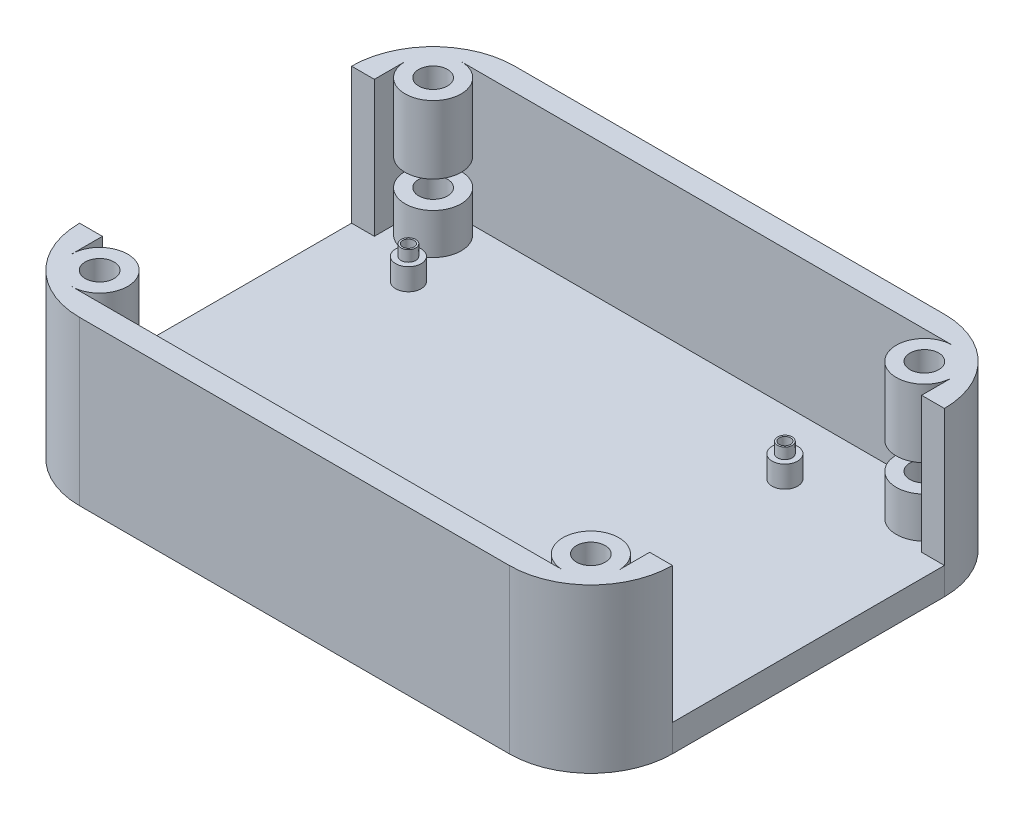
SolidWorks part; units mm, degrees
ref_plane "Front Plane" through (0, 0, 0) normal (0, 0, 1) x (1, 0, 0)
ref_plane "Top Plane" through (0, 0, 0) normal (0, 1, 0) x (1, 0, 0)
ref_plane "Right Plane" through (0, 0, 0) normal (1, 0, 0) x (0, 0, -1)
sketch "Sketch1" plane through (0, 0, 0) normal (0, 1, 0) x (1, 0, 0)
  line L0 (-39.5, 33) -> (39.5, 33)
  line L1 (-39.5, 28) -> (39.5, 28)
  line L2 (-42.5, 25) -> (-42.5, -25)
  line L3 (-39.5, -28) -> (39.5, -28)
  line L4 (42.5, 25) -> (42.5, -25)
  line L5 (-42.5, 28) -> (42.5, -28) construction
  line L6 (-42.5, -28) -> (42.5, 28) construction
  line L7 (47.5, 25) -> (47.5, -25)
  line L8 (-39.5, -33) -> (39.5, -33)
  line L9 (-47.5, 25) -> (-47.5, -25)
  line L10 (-39.5, 40) -> (39.5, 40)
  line L11 (54.5, 25) -> (54.5, -25)
  line L12 (-39.5, -40) -> (39.5, -40)
  line L13 (-54.5, 25) -> (-54.5, -25)
  arc A0 (-42.5, -25) -> (-39.5, -28) centre (-39.5, -25) ccw
  arc A1 (39.5, -28) -> (42.5, -25) centre (39.5, -25) ccw
  arc A2 (39.5, 28) -> (42.5, 25) centre (39.5, 25) cw
  arc A3 (-39.5, 28) -> (-42.5, 25) centre (-39.5, 25) ccw
  arc A4 (39.5, 33) -> (47.5, 25) centre (39.5, 25) cw
  arc A5 (39.5, -33) -> (47.5, -25) centre (39.5, -25) ccw
  arc A6 (-47.5, -25) -> (-39.5, -33) centre (-39.5, -25) ccw
  arc A7 (-39.5, 33) -> (-47.5, 25) centre (-39.5, 25) ccw
  arc A8 (39.5, 40) -> (54.5, 25) centre (39.5, 25) cw
  arc A9 (39.5, -40) -> (54.5, -25) centre (39.5, -25) ccw
  arc A10 (-54.5, -25) -> (-39.5, -40) centre (-39.5, -25) ccw
  arc A11 (-39.5, 40) -> (-54.5, 25) centre (-39.5, 25) ccw
  point P0 (0, 0)
  point P9 (0, 0)
  dimension "D3" = 3
  dimension "D1" = 85
  dimension "D2" = 56
  dimension "D4" = 5
  dimension "D5" = 7
extrude "Boss-Extrude1" add sketch "Sketch1" along normal blind 5 contours L0 A7 L9 A6 L8 A5 L7 A4 A3 L1 A2 L4 A1 L3 A0 L2 | L10 A11 L13 A10 L12 A9 L11 A8 A7 L0 A4 L7 A5 L8 A6 L9 | L2 A0 L3 A1 L4 A2 L1 A3 region at (0, 0, -31.8432) region at (0, 0, -38.6479)
sketch "Sketch4" plane through (0, 0, 0) normal (0, 1, 0) x (1, 0, 0)
  line L0 (-50.1066, 35.6066) -> (50.1066, -35.6066) construction
  line L1 (-17.5, 17.5) -> (17.5, 17.5) construction
  line L2 (-17.5, 17.5) -> (-17.5, -17.5) construction
  line L3 (-17.5, -17.5) -> (17.5, -17.5) construction
  line L4 (17.5, 17.5) -> (17.5, -17.5) construction
  line L5 (-17.5, 17.5) -> (17.5, -17.5) construction
  line L6 (-17.5, -17.5) -> (17.5, 17.5) construction
  line L7 (-50.1066, -35.6066) -> (50.1066, 35.6066) construction
  line L8 (-37.5, 26.6481) -> (-37.5, -26.6481) construction
  line L9 (-37.5, -26.6481) -> (37.5, -26.6481) construction
  line L10 (37.5, -26.6481) -> (37.5, 26.6481) construction
  line L11 (37.5, 26.6481) -> (-37.5, 26.6481) construction
  circle A0 centre (0, 0) radius 3.1
  circle A1 centre (17.5, -17.5) radius 3.1
  circle A2 centre (-17.5, -17.5) radius 3.1
  circle A3 centre (-17.5, 17.5) radius 3.1
  circle A4 centre (17.5, 17.5) radius 3.1
  circle A5 centre (-17.5, 0) radius 3.1
  circle A6 centre (0, 17.5) radius 3.1
  circle A7 centre (17.5, 0) radius 3.1
  circle A8 centre (0, -17.5) radius 3.1
  arc A9 (-39.5, 40) -> (-54.5, 25) centre (-39.5, 25) ccw construction
  arc A10 (39.5, -40) -> (54.5, -25) centre (39.5, -25) ccw construction
  arc A11 (-54.5, -25) -> (-39.5, -40) centre (-39.5, -25) ccw construction
  arc A12 (54.5, 25) -> (39.5, 40) centre (39.5, 25) ccw construction
  circle A13 centre (-37.5, 26.6481) radius 3.1
  circle A14 centre (37.5, 26.6481) radius 3.1
  circle A15 centre (-37.5, -26.6481) radius 3.1
  circle A16 centre (37.5, -26.6481) radius 3.1
  point P0 (0, 0)
  dimension "D1" = 6.2
  dimension "D2" = 6.2
  dimension "D3" = 6.2
  dimension "D4" = 6.2
  dimension "D5" = 6.2
  dimension "D7" = 6.2
  dimension "D8" = 6.2
  dimension "D9" = 6.2
  dimension "D10" = 6.2
  dimension "D11" = 6.2
  dimension "D12" = 6.2
  dimension "D13" = 6.2
  dimension "D14" = 6.2
  dimension "D6" = 35
  dimension "D15" = 75
extrude "Cut-Extrude1" cut sketch "Sketch4" along normal blind 4 contours A15 | A16 | A14 | A13 | A5 | A8 | A7 | A6 | A3 | A4 | A1 | A2 | A0 region at (-17.5, 0, 0) region at (0, 0, -17.5) region at (17.5, 0, 0) region at (0, 0, 17.5) region at (-37.5, 0, -26.6481) region at (37.5, 0, -26.6481) region at (-37.5, 0, 26.6481) region at (37.5, 0, 26.6481)
extrude "Boss-Extrude3" add sketch "Sketch1<3>" along normal blind 30 contours L10 A11 L13 A10 L12 A9 L11 A8 A7 L0 A4 L7 A5 L8 A6 L9 region at (0, 0, -38.6479)
sketch "Sketch1<3>" plane through (0, 0, 0) normal (0, 1, 0) x (1, 0, 0) same geometry as "Sketch1"
sketch "Sketch7" plane through (-54.5, 0, 0) normal (-1, 0, 0) x (0, 0, 1)
  line L0 (-20, 30) -> (-25, 30)
  line L1 (-25, 30) -> (-25, 0) construction
  line L2 (20, 30) -> (25, 30)
  line L3 (25, 30) -> (25, 0) construction
  line L4 (20, 5) -> (25, 5)
  line L5 (-20, 5) -> (-25, 5)
  line L6 (-25, 30) -> (-25, 5)
  line L7 (25, 30) -> (25, 5)
  line L8 (-25, 30) -> (25, 30) construction
  line L14 (-20, 5) -> (20, 5)
  line L15 (20, 5) -> (20, 25)
  line L16 (20, 25) -> (-20, 25)
  line L17 (-20, 25) -> (-20, 5)
  line L18 (-20, 5) -> (20, 5)
  line L20 (20, 30) -> (-20, 30)
  dimension "D1" = 5
extrude "Cut-Extrude2" cut sketch "Sketch7" against normal through all both and the other way through all
sketch "Sketch3" plane through (0, 0, 0) normal (0, 1, 0) x (1, 0, 0)
  line L0 (-40, 0) -> (26.04, 0) construction
  line L1 (-40, -20.955) -> (-40, 20.955) construction
  line L2 (26.04, -24.13) -> (26.04, 24.13) construction
  line L3 (-47.5, 25) -> (-47.5, -25) construction
  line L4 (-47.5, 0) -> (-40, 0) construction
  circle A0 centre (-40, 20.955) radius 1.35
  circle A1 centre (-40, -20.955) radius 1.35
  circle A2 centre (26.04, 24.13) radius 1.35
  circle A3 centre (26.04, -24.13) radius 1.35
  circle A4 centre (-40, -20.955) radius 1.05
  circle A5 centre (-40, 20.955) radius 1.05
  circle A6 centre (26.04, 24.13) radius 1.05
  circle A7 centre (26.04, -24.13) radius 1.05
  arc A8 (-47.5, -25) -> (-39.5, -33) centre (-39.5, -25) ccw construction
  arc A9 (-47.5, -25) -> (-39.5, -33) centre (-39.5, -25) ccw
  arc A10 (-39.5, 33) -> (-47.5, 25) centre (-39.5, 25) ccw construction
  arc A11 (-39.5, 33) -> (-47.5, 25) centre (-39.5, 25) ccw
  point P4 (-6.98, 0)
  point P8 (-40, 0)
  point P13 (26.04, 0)
  dimension "D4" = 2.7
  dimension "D5" = 2.7
  dimension "D6" = 2.7
  dimension "D7" = 2.7
  dimension "D9" = 2.1
  dimension "D10" = 2.1
  dimension "D11" = 2.1
  dimension "D12" = 2.1
  dimension "D1" = 66.04
  dimension "D2" = 48.26
  dimension "D3" = 41.91
  dimension "D8" = 7.5
extrude "Boss-Extrude2" add sketch "Sketch3" along normal blind 6 from surface contours A2 | A0 | A1 | A3 | A7 | A4 | A5 region at (24.7282, 0, -24.13) starting at face at (0, 5, 0)
sketch "Sketch8" plane through (0, 0, 0) normal (0, 1, 0) x (1, 0, 0)
  line L0 (0, 40) -> (0, 33) construction
  line L1 (-39.5, 40) -> (39.5, 40) construction
  line L2 (39.5, 33) -> (-39.5, 33) construction
  line L3 (-5, 36.5) -> (5, 36.5) construction
  circle A0 centre (5, 36.5) radius 3.1
  circle A1 centre (-5, 36.5) radius 2
  point P10 (0, 36.5)
  dimension "D2" = 6.2
  dimension "D3" = 4
  dimension "D1" = 10
sketch "Sketch13" plane through (0, 5, 0) normal (0, 1, 0) x (1, 0, 0)
  circle A0 centre (26.04, 24.13) radius 1.35 construction
  circle A1 centre (26.04, -24.13) radius 1.35 construction
  circle A2 centre (-40, -20.955) radius 1.35 construction
  circle A3 centre (-40, 20.955) radius 1.35 construction
  circle A4 centre (26.04, 24.13) radius 1.35
  circle A5 centre (26.04, -24.13) radius 1.35
  circle A6 centre (-40, -20.955) radius 1.35
  circle A7 centre (-40, 20.955) radius 1.35
  circle A8 centre (26.04, 24.13) radius 2.35
  circle A9 centre (26.04, -24.13) radius 2.35
  circle A10 centre (-40, -20.955) radius 2.35
  circle A11 centre (-40, 20.955) radius 2.35
  dimension "D1" = 1
  dimension "D2" = 1
extrude "Boss-Extrude8" add sketch "Sketch13" along normal blind 4
sketch "Sketch14" plane through (0, 30, 0) normal (0, 1, 0) x (1, 0, 0)
  line L0 (-40.0069, 30.6569) -> (40.0069, 30.6569)
  line L1 (-45.1569, 35.8069) -> (45.1569, 35.8069)
  line L2 (-45.1569, -35.8069) -> (45.1569, -35.8069)
  line L3 (-40.0069, -30.6569) -> (40.0069, -30.6569)
  line L4 (-50.3069, 30.6569) -> (-50.3069, -30.6569)
  line L5 (-45.1569, 25.5069) -> (-45.1569, -25.5069)
  line L6 (50.3069, 30.6569) -> (50.3069, -30.6569)
  line L7 (45.1569, 25.5069) -> (45.1569, -25.5069)
  circle A0 centre (-45.1569, 30.6569) radius 2.65
  arc A1 (-39.5, 33) -> (-47.5, 25) centre (-39.5, 25) ccw construction
  circle A2 centre (-45.1569, -30.6569) radius 2.65
  arc A3 (-47.5, -25) -> (-39.5, -33) centre (-39.5, -25) ccw construction
  circle A4 centre (45.1569, 30.6569) radius 2.65
  arc A5 (47.5, 25) -> (39.5, 33) centre (39.5, 25) ccw construction
  circle A6 centre (45.1569, -30.6569) radius 2.65
  arc A7 (39.5, -33) -> (47.5, -25) centre (39.5, -25) ccw construction
  circle A8 centre (-45.1569, 30.6569) radius 5.15
  circle A9 centre (-45.1569, -30.6569) radius 5.15
  circle A10 centre (45.1569, -30.6569) radius 5.15
  circle A11 centre (45.1569, 30.6569) radius 5.15
  line M4 (54.5, -25) -> (47.5, -25)
  arc M5 (47.5, -25) -> (39.5, -33) centre (39.5, -25) cw
  line M6 (39.5, -33) -> (-39.5, -33)
  arc M7 (-39.5, -33) -> (-47.5, -25) centre (-39.5, -25) cw
  line M8 (-47.5, -25) -> (-54.5, -25)
  dimension "D1" = 5.3
  dimension "D2" = 5.3
  dimension "D3" = 5.3
  dimension "D4" = 5.3
  dimension "D5" = 2.5
  dimension "D6" = 2.5
  dimension "D7" = 2.5
  dimension "D8" = 2.5
extrude "Boss-Extrude9" add sketch "Sketch14" against normal up to surface (25 mm away) contours A8 A0 | A9 A2 M7 | A9 A2 M7 | A11 A4 | A10 A6 M5 | A10 A6 M5 region at (-41.6183, 30, -27.1183) region at (41.6183, 30, -34.1955) region at (-43.0657, 30, 28.5657) region at (43.0657, 30, 28.5657) region at (-49.4123, 30, 28.0093) region at (48.7008, 30, 34.2008) up to face at (-40, 5, 23.305)
extrude "Cut-Extrude4" cut sketch "Sketch14<3>" against normal up to surface (25 mm away) contours A0 | A2 M7 | A4 | A6 M5 | A10 A9 L2 M5 M6 M7 | A11 L1 A8 L0 | A10 L3 A9 M7 M6 M5 | A9 L5 A8 L4 M8 M7 | A11 L7 A10 L6 M5 M4 | A10 L6 M4 M5 | A9 L4 M7 M8 region at (0, 30, -33.2702) region at (-47.7547, 30, -0.6628) region at (47.7547, 30, -0.6628) region at (-49.2401, 30, 26.4194) region at (0, 30, 31.8308) region at (49.2401, 30, 26.4194) region at (0, 30, 34.4226) region at (-45.8936, 30, 31.3936) region at (45.8936, 30, 31.3936) region at (-45.1569, 30, -30.6569) region at (45.1569, 30, -30.6569) up to face at (0, 5, 0)
sketch "Sketch14<3>" plane through (0, 30, 0) normal (0, 1, 0) x (1, 0, 0) same geometry as "Sketch14"
extrude "Cut-Extrude5" cut sketch "Sketch14<4>" against normal up to surface (30 mm away) contours A0 | A4 | A6 M5 | A6 M5 | A2 M7 | A2 M7 region at (-45.8936, 30, 31.3936) region at (-44.3083, 30, 29.8083) region at (44.3083, 30, 29.8083) region at (45.8936, 30, 31.3936) region at (-45.1569, 30, -30.6569) region at (45.1569, 30, -30.6569) up to face at (-17.5, 0, -14.4)
sketch "Sketch14<4>" plane through (0, 30, 0) normal (0, 1, 0) x (1, 0, 0) same geometry as "Sketch14"
ref_plane "Plane1" through (0, 15, 0) normal (0, 1, 0) x (1, 0, 0)
extrude "Cut-Extrude6" cut sketch "Sketch14<6>" against normal blind 2.5 and the other way blind 2.5 from surface contours A10 A6 M5 | A10 A6 M5 | A11 A4 | A8 A0 | A9 A2 M7 | A9 A2 M7 region at (-41.6183, 30, -27.1183) region at (41.6183, 30, -34.1955) region at (-43.0657, 30, 28.5657) region at (43.0657, 30, 28.5657) region at (-49.4123, 30, 28.0093) region at (48.7008, 30, 34.2008) starting at plane "Plane1"
sketch "Sketch14<6>" plane through (0, 30, 0) normal (0, 1, 0) x (1, 0, 0) same geometry as "Sketch14"
